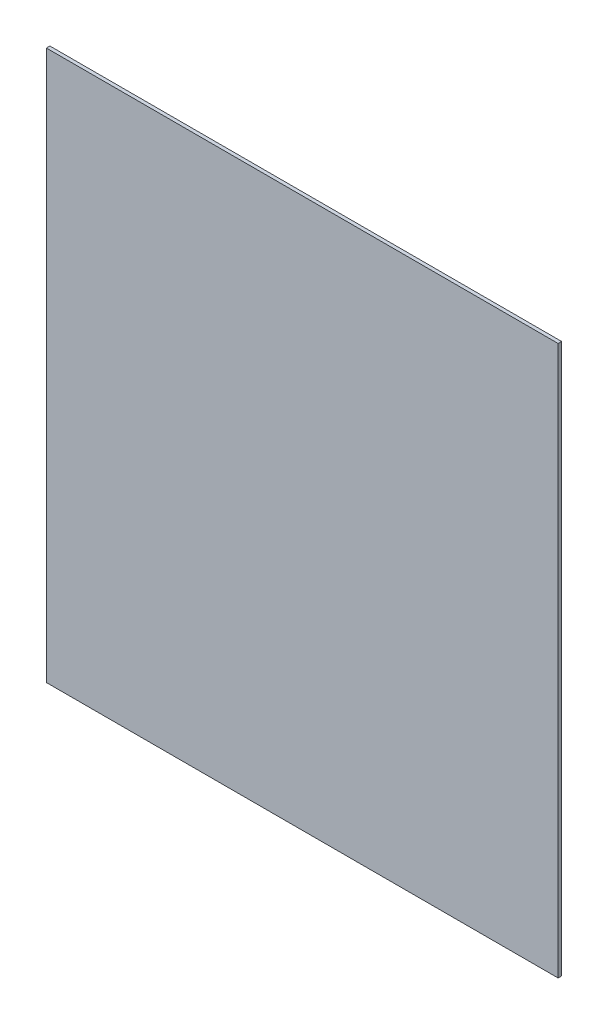
SolidWorks part; units mm, degrees
material "Perspex (TM) GS Acrylic Cast Sheet"
ref_plane "Front Plane" through (0, 0, 0) normal (0, 0, 1) x (1, 0, 0)
ref_plane "Top Plane" through (0, 0, 0) normal (0, 1, 0) x (1, 0, 0)
ref_plane "Right Plane" through (0, 0, 0) normal (1, 0, 0) x (0, 0, -1)
sketch "Sketch1" plane through (0, 0, 0) normal (0, 0, 1) x (1, 0, 0)
  line L1 (0, 0) -> (437.65, 0)
  line L2 (0, 0) -> (0, 470)
  line L3 (0, 470) -> (437.65, 470)
  line L4 (437.65, 0) -> (437.65, 470)
  dimension "D1" = 437.65
  dimension "D2" = 470
extrude "Boss-Extrude1" add sketch "Sketch1" along normal blind 3
